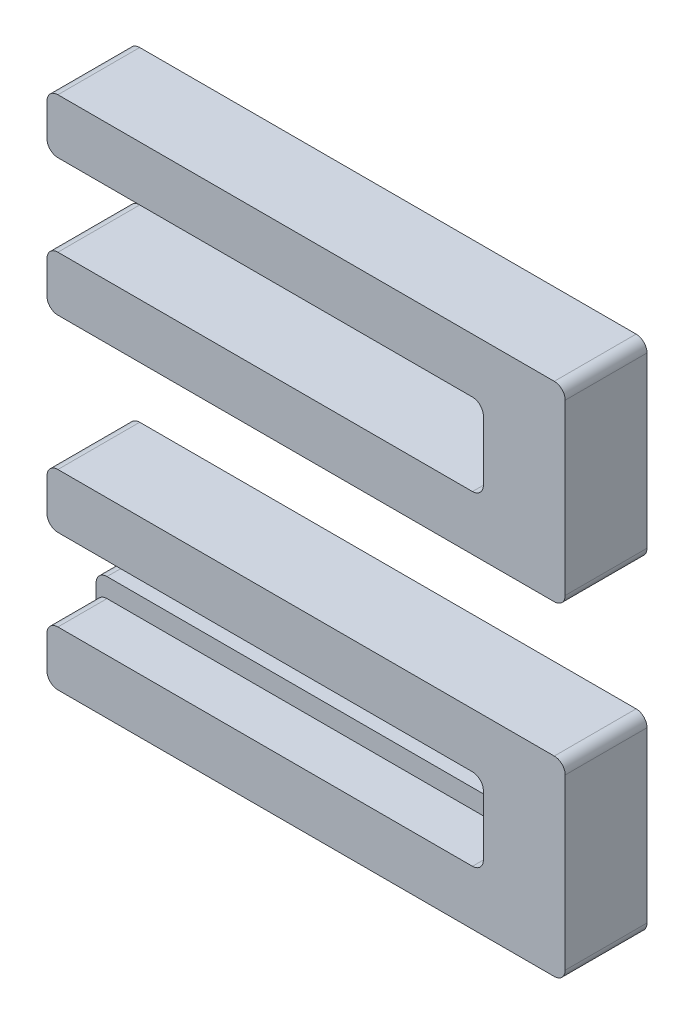
SolidWorks part; units mm, degrees
ref_plane "Front Plane" through (0, 0, 0) normal (0, 0, 1) x (1, 0, 0)
ref_plane "Top Plane" through (0, 0, 0) normal (0, 1, 0) x (1, 0, 0)
ref_plane "Right Plane" through (0, 0, 0) normal (1, 0, 0) x (0, 0, -1)
sketch "Sketch2" plane through (0, 0, 0) normal (0, 0, 1) x (1, 0, 0)
  line L0 (-2.7742, -2.4497) -> (31.3823, -2.4497) construction
  line L1 (0, 0) -> (19, 0)
  line L2 (0, 0) -> (0, 7)
  line L3 (0, 7) -> (19, 7)
  line L4 (19, 0) -> (19, 7)
  line L5 (0, 5) -> (16, 5)
  line L6 (0, 5) -> (0, 2)
  line L7 (0, 2) -> (16, 2)
  line L8 (16, 5) -> (16, 2)
  line L9 (0, 5) -> (16, 5)
  line L10 (0, 5) -> (0, 4.3)
  line L11 (0, 4.3) -> (16, 4.3)
  line L12 (16, 5) -> (16, 4.3)
  line L13 (16, -9.8995) -> (16, -9.1995)
  line L14 (0, -9.1995) -> (16, -9.1995)
  line L15 (0, -9.8995) -> (0, -9.1995)
  line L16 (0, -9.8995) -> (16, -9.8995)
  line L17 (16, -9.8995) -> (16, -6.8995)
  line L18 (0, -6.8995) -> (16, -6.8995)
  line L19 (0, -9.8995) -> (0, -6.8995)
  line L20 (0, -9.8995) -> (16, -9.8995)
  line L21 (19, -4.8995) -> (19, -11.8995)
  line L22 (0, -11.8995) -> (19, -11.8995)
  line L23 (0, -4.8995) -> (0, -11.8995)
  line L24 (0, -4.8995) -> (19, -4.8995)
  dimension "D1" = 7
  dimension "D2" = 3
  dimension "D3" = 2
  dimension "D4" = 3
  dimension "D5" = 16
  dimension "D6" = 2.3
extrude "Boss-Extrude1" add sketch "Sketch2" along normal blind 3 contours L5 L8 L7 L2 L1 L4 L3 | L24 L23 L18 L17 L13 L16 L22 L21 region at (0.2025, 1, 0) region at (16.2025, -9.5495, 0)
extrude "Boss-Extrude3" add sketch "Sketch2<4>" along normal blind 1.2 contours L15 L16 L13 L14 | L6 L11 L8 L5 region at (8, 4.65, 0) region at (8, -9.5495, 0)
sketch "Sketch2<4>" plane through (0, 0, 0) normal (0, 0, 1) x (1, 0, 0) same geometry as "Sketch2"
fillet "Fillet2" radius 0.4 10 edges at (0, 5, 2.1) (16, 2, 1.5) (16, 4.3, 0.6) (16, 5, 2.1) (19, 7, 1.5) (19, 0, 1.5) (0, 0, 1.5) (0, 2, 1.5) (0, 4.3, 0.6) (0, 7, 1.5)
fillet "Fillet3" radius 0.4 10 edges at (19, -11.8995, 1.5) (19, -4.8995, 1.5) (16, -6.8995, 1.5) (16, -9.8995, 2.1) (16, -9.1995, 0.6) (0, -11.8995, 1.5) (0, -9.8995, 2.1) (0, -9.1995, 0.6) (0, -4.8995, 1.5) (0, -6.8995, 1.5)
